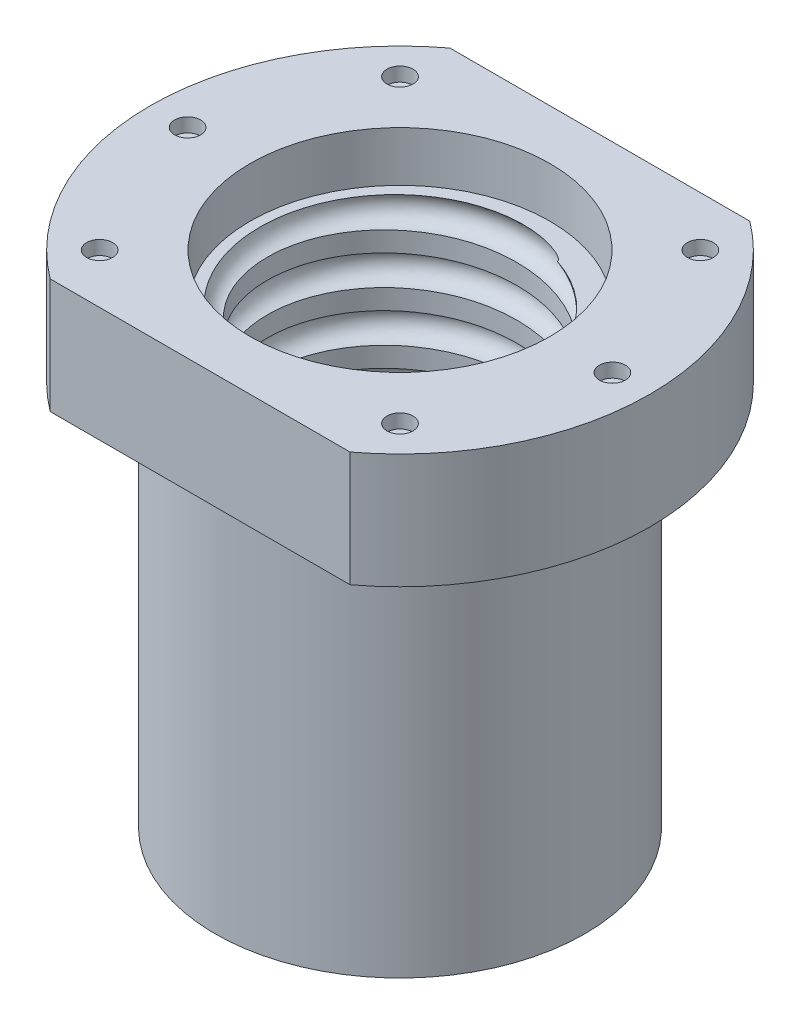
SolidWorks part; units mm, degrees
ref_plane "Front Plane" through (0, 0, 0) normal (0, 0, 1) x (1, 0, 0)
ref_plane "Top Plane" through (0, 0, 0) normal (0, 1, 0) x (1, 0, 0)
ref_plane "Right Plane" through (0, 0, 0) normal (1, 0, 0) x (0, 0, -1)
sketch "Sketch1" plane through (0, 0, 0) normal (0, 0, 1) x (1, 0, 0)
  line L0 (0, -128.5336) -> (0, 128.5336) construction
  line L2 (-15, 98.1223) -> (-25, 98.1223)
  line L3 (-25, 98.1223) -> (-25, 86.6223)
  line L4 (-25, 86.6223) -> (-18.5, 86.6223)
  line L5 (-18.5, 86.6223) -> (-18.5, 48.1223)
  line L6 (-18.5, 48.1223) -> (-16, 48.1223)
  line L7 (-16, 48.1223) -> (-16, 53.1223)
  line L8 (-16, 53.1223) -> (-12.5, 53.1223)
  line L9 (-12.5, 53.1223) -> (-12.5, 93.1223)
  line L10 (-12.5, 93.1223) -> (-15, 93.1223)
  line L11 (-15, 93.1223) -> (-15, 98.1223)
  point P4 (0, 0)
  point P8 (0, 0)
  dimension "D1" = 10
  dimension "D2" = 12.5
  dimension "D3" = 2.5
  dimension "D4" = 2.5
  dimension "D5" = 6
  dimension "D6" = 11.5
  dimension "D7" = 38.5
  dimension "D8" = 5
  dimension "D9" = 5
revolve "Revolve1" add sketch "Sketch1" angle 360 about L0
sketch "Sketch3" plane through (0, 98.1223, 0) normal (0, 1, 0) x (1, 0, 0)
  line L1 (-16.6132, -20) -> (16.6132, -20)
  line L3 (-16.6132, 20) -> (16.6132, 20)
  arc A1 (-16.6132, -20) -> (16.6132, -20) centre (0, 0) ccw
  arc A2 (16.6132, 20) -> (-16.6132, 20) centre (0, 0) ccw
extrude "Cut-Extrude2" cut sketch "Sketch3" against normal through all both and the other way through all contours A1 L1 | A2 L3
sketch "Sketch4" plane through (0, 98.1223, 0) normal (0, 1, 0) x (1, 0, 0)
  circle A10 centre (-21.25, 0) radius 0.7
  circle A11 centre (-15.026, 15.026) radius 0.7
  circle A13 centre (15.026, 15.026) radius 0.7
  circle A14 centre (21.25, 0) radius 0.7
  circle A15 centre (15.026, -15.026) radius 0.7
  circle A18 centre (-15.026, -15.026) radius 0.7
  circle A19 centre (0, -21.25) radius 0.7 [skipped]
  circle A20 centre (0, 21.25) radius 0.7 [skipped]
  point P6 (0, 0)
  point P25 (0, 0)
  dimension "D1" = 8
extrude "Cut-Extrude3" cut sketch "Sketch4" against normal through all both and the other way through all
sketch "Sketch6" plane through (0, 98.1223, 0) normal (0, 1, 0) x (1, 0, 0)
  circle A1 centre (-21.25, 0) radius 1.3
  circle A2 centre (-15.026, 15.026) radius 1.3
  circle A4 centre (15.026, 15.026) radius 1.3
  circle A5 centre (21.25, 0) radius 1.3
  circle A6 centre (15.026, -15.026) radius 1.3
  circle A8 centre (-15.026, -15.026) radius 1.3
  circle A9 centre (0, -21.25) radius 1.3 [skipped]
  circle A10 centre (0, 21.25) radius 1.3 [skipped]
  dimension "D1" = 8
extrude "Cut-Extrude4" cut sketch "Sketch6" against normal blind 1.4
sketch "Sketch7" plane through (0, 93.1223, 0) normal (0, 1, 0) x (1, 0, 0)
  circle A0 centre (0, 0) radius 12.5 construction
  circle A1 centre (0, 0) radius 12.5
curve "Helix/Spiral1" pitch 5 height 50 turns 10
ref_plane "Plane1" through (0, 0, 0) normal (0, 0, 1) x (1, 0, 0)
sketch "Sketch8" plane through (0, 0, 0) normal (0, 0, 1) x (1, 0, 0)
  circle A0 centre (-12.5, 93.1223) radius 1.5
  spline S0 degree 3 poles (-12.5, 93.1223) (-12.5, 93.0188) (-11.8491, 92.8094) (-9.0689, 92.4973) (-4.9081, 92.1847) (0, 91.8723) (4.9081, 91.5598) (9.0689, 91.2473) (11.8491, 90.9348) (12.8254, 90.6223) (11.8491, 90.3098) (9.0689, 89.9973) (3.5211, 89.5806) (-3.5211, 89.1639) (-9.0689, 88.7473) (-11.8491, 88.4348) (-12.8254, 88.1223) (-11.8491, 87.8098) (-9.0689, 87.4973) (-3.5211, 87.0806) (3.5211, 86.6639) (9.0689, 86.2473) (11.8491, 85.9348) (12.8254, 85.6223) (11.8491, 85.3098) (9.0689, 84.9973) (3.5211, 84.5806) (-3.5211, 84.1639) (-9.0689, 83.7473) (-11.8491, 83.4348) (-12.8254, 83.1223) (-11.8491, 82.8098) (-9.0689, 82.4973) (-3.5211, 82.0806) (3.5211, 81.6639) (9.0689, 81.2473) (11.8491, 80.9348) (12.8254, 80.6223) (11.8491, 80.3098) (9.0689, 79.9973) (3.5211, 79.5806) (-3.5211, 79.1639) (-9.0689, 78.7473) (-11.8491, 78.4348) (-12.8254, 78.1223) (-11.8491, 77.8098) (-9.0689, 77.4973) (-3.5211, 77.0806) (3.5211, 76.6639) (9.0689, 76.2473) (11.8491, 75.9348) (12.8254, 75.6223) (11.8491, 75.3098) (9.0689, 74.9973) (3.5211, 74.5806) (-3.5211, 74.1639) (-9.0689, 73.7473) (-11.8491, 73.4348) (-12.8254, 73.1223) (-11.8491, 72.8098) (-9.0689, 72.4973) (-3.5211, 72.0806) (3.5211, 71.6639) (9.0689, 71.2473) (11.8491, 70.9348) (12.8254, 70.6223) (11.8491, 70.3098) (9.0689, 69.9973) (3.5211, 69.5806) (-3.5211, 69.1639) (-9.0689, 68.7473) (-11.8491, 68.4348) (-12.8254, 68.1223) (-11.8491, 67.8098) (-9.0689, 67.4973) (-3.5211, 67.0806) (3.5211, 66.6639) (9.0689, 66.2473) (11.8491, 65.9348) (12.8254, 65.6223) (11.8491, 65.3098) (9.0689, 64.9973) (3.5211, 64.5806) (-3.5211, 64.1639) (-9.0689, 63.7473) (-11.8491, 63.4348) (-12.8254, 63.1223) (-11.8491, 62.8098) (-9.0689, 62.4973) (-3.5211, 62.0806) (3.5211, 61.6639) (9.0689, 61.2473) (11.8491, 60.9348) (12.8254, 60.6223) (11.8491, 60.3098) (9.0689, 59.9973) (3.5211, 59.5806) (-3.5211, 59.1639) (-9.0689, 58.7473) (-11.8491, 58.4348) (-12.8254, 58.1223) (-11.8491, 57.8098) (-9.0689, 57.4973) (-3.5211, 57.0806) (3.5211, 56.6639) (9.0689, 56.2473) (11.8491, 55.9348) (12.8254, 55.6223) (11.8491, 55.3098) (9.0689, 54.9973) (3.5211, 54.5806) (-3.5211, 54.1639) (-9.0689, 53.7473) (-11.8491, 53.4348) (-12.8254, 53.1223) (-11.8491, 52.8098) (-9.0689, 52.4973) (-3.5211, 52.0806) (3.5211, 51.6639) (9.0689, 51.2473) (11.8491, 50.9348) (12.8254, 50.6223) (11.8491, 50.3098) (9.0689, 49.9973) (3.5211, 49.5806) (-3.5211, 49.1639) (-9.0689, 48.7473) (-11.8491, 48.4348) (-12.8254, 48.1223) (-11.8491, 47.8098) (-9.0689, 47.4973) (-3.5211, 47.0806) (3.5211, 46.6639) (9.0689, 46.2473) (11.8491, 45.9348) (12.8254, 45.6223) (11.8491, 45.3098) (9.0689, 44.9973) (4.9081, 44.6848) (0, 44.3722) (-4.9081, 44.0598) (-9.0689, 43.7472) (-11.8491, 43.4351) (-12.5, 43.2258) (-12.5, 43.1223) knots 0 0 0 0 0.00625 0.0125 0.01875 0.025 0.03125 0.0375 0.04375 0.05 0.05625 0.0625 0.06875 0.08125 0.0875 0.09375 0.1 0.10625 0.1125 0.11875 0.13125 0.1375 0.14375 0.15 0.15625 0.1625 0.16875 0.18125 0.1875 0.19375 0.2 0.20625 0.2125 0.21875 0.23125 0.2375 0.24375 0.25 0.25625 0.2625 0.26875 0.28125 0.2875 0.29375 0.3 0.30625 0.3125 0.31875 0.33125 0.3375 0.34375 0.35 0.35625 0.3625 0.36875 0.38125 0.3875 0.39375 0.4 0.40625 0.4125 0.41875 0.43125 0.4375 0.44375 0.45 0.45625 0.4625 0.46875 0.48125 0.4875 0.49375 0.5 0.50625 0.5125 0.51875 0.53125 0.5375 0.54375 0.55 0.55625 0.5625 0.56875 0.58125 0.5875 0.59375 0.6 0.60625 0.6125 0.61875 0.63125 0.6375 0.64375 0.65 0.65625 0.6625 0.66875 0.68125 0.6875 0.69375 0.7 0.70625 0.7125 0.71875 0.73125 0.7375 0.74375 0.75 0.75625 0.7625 0.76875 0.78125 0.7875 0.79375 0.8 0.80625 0.8125 0.81875 0.83125 0.8375 0.84375 0.85 0.85625 0.8625 0.86875 0.88125 0.8875 0.89375 0.9 0.90625 0.9125 0.91875 0.93125 0.9375 0.94375 0.95 0.95625 0.9625 0.96875 0.975 0.98125 0.9875 0.99375 1 1 1 1 construction
  dimension "D1" = 3
sweep "Cut-Sweep1" cut profiles "Sketch8" path "Helix/Spiral1" align with end faces yes
